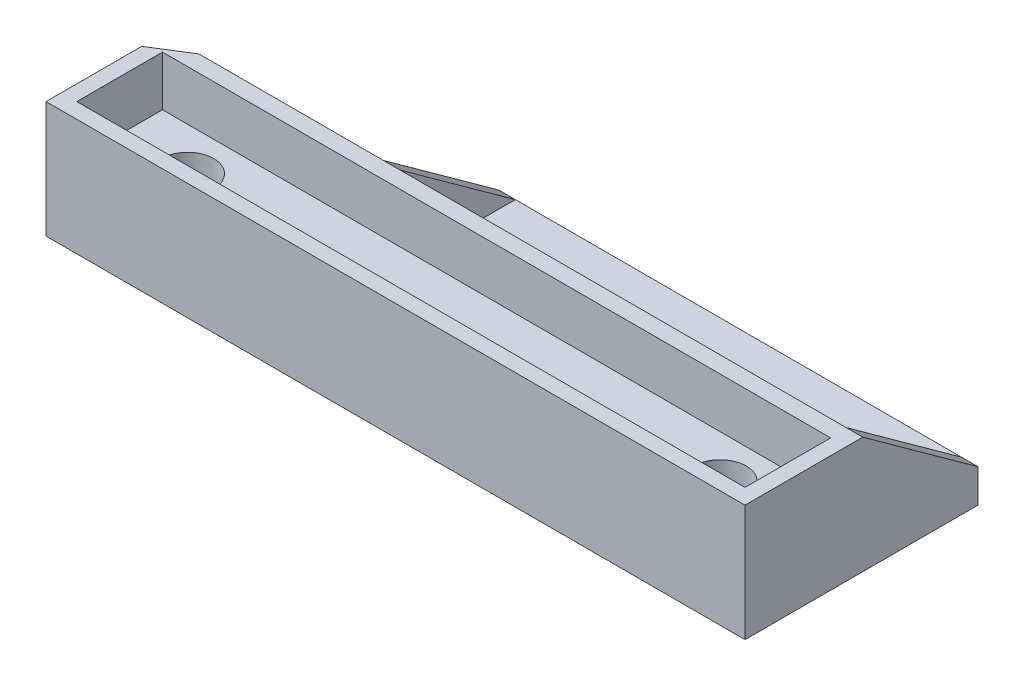
SolidWorks part; units mm, degrees
ref_plane "Front Plane" through (0, 0, 0) normal (0, 0, 1) x (1, 0, 0)
ref_plane "Top Plane" through (0, 0, 0) normal (0, 1, 0) x (1, 0, 0)
ref_plane "Right Plane" through (0, 0, 0) normal (1, 0, 0) x (0, 0, -1)
sketch "Sketch1" plane through (0, 0, 0) normal (0, 1, 0) x (1, 0, 0)
  line L1 (2.0004, 7) -> (42, 7)
  line L2 (0, 5.75) -> (0, 0)
  line L3 (0, 0) -> (42, 0)
  line L4 (42, 7) -> (42, 0)
  line L6 (0, 5.75) -> (2.0004, 7)
  dimension "D1" = 32
  dimension "D2" = 42
  dimension "D3" = 7
  dimension "D4" = 5.75
extrude "Riser" add sketch "Sketch1" along normal blind 7
sketch "Sketch2" plane through (0, 0, 0) normal (0, -1, 0) x (1, 0, 0)
  line L1 (21, 0) -> (21, -7) construction
  line L2 (0, 0) -> (42, 0) construction
  line L4 (42, -7) -> (2.0004, -7) construction
  line L5 (42, 0) -> (42, -7) construction
  circle A0 centre (37, -3.5) radius 1.575
  circle A2 centre (5, -3.5) radius 1.575
  point P6 (42, -3.5)
  dimension "D2" = 3.15
  dimension "D1" = 5
extrude "Mounting Holes" cut sketch "Sketch2" against normal through all
sketch "Sketch3" plane through (0, 7, 0) normal (0, 1, 0) x (1, 0, 0)
  line L5 (42, 7) -> (2.0004, 7) construction
  line L12 (0.925, 6.075) -> (41.075, 6.075)
  line L13 (0.925, 6.075) -> (0.925, 0.925)
  line L14 (0.925, 0.925) -> (41.075, 0.925)
  line L15 (41.075, 6.075) -> (41.075, 0.925)
  line L16 (42, 0) -> (42, 7) construction
  dimension "D1" = 5.15
  dimension "D2" = 40.15
  dimension "D3" = 0.925
  dimension "D4" = 0.925
extrude "Recess" cut sketch "Sketch3" against normal blind 3 contours L12 L15 L14 L13
sketch "Sketch4" plane through (0, 0, 0) normal (0, 1, 0) x (1, 0, 0)
  line L0 (-7.0926, 1.318) -> (28.8348, 23.768) construction
  line L1 (2.0004, 7) -> (42, 7)
  line L2 (42, 7) -> (42, 14)
  line L3 (42, 14) -> (13.2028, 14)
  line L4 (13.2028, 14) -> (2.0004, 7)
  dimension "D1" = 32
  dimension "D2" = 7
extrude "Flange" add sketch "Sketch4" along normal blind 7
sketch "Sketch5" plane through (0, 7, 0) normal (0, 1, 0) x (1, 0, 0)
  line L0 (14.2028, 7.075) -> (14.2028, 14)
  line L1 (42, 14) -> (13.2028, 14) construction
  line L2 (14.2028, 14) -> (41, 14)
  line L3 (41, 14) -> (41, 7.075)
  line L4 (41, 7.075) -> (14.2028, 7.075)
  line L5 (2.1204, 7.075) -> (13.2028, 7.075)
  line L6 (0.925, 6.075) -> (41.075, 6.075) construction
  line L7 (42, 0) -> (42, 14) construction
  line L8 (13.2028, 14) -> (0, 5.75) construction
  line L9 (13.2028, 7.075) -> (13.2028, 14)
  line L10 (13.2028, 14) -> (2.1204, 7.075)
  dimension "D2" = 1
  dimension "D3" = 1
  dimension "D4" = 1
extrude "Flange Cutout" cut sketch "Sketch5" against normal blind 5
sketch "Sketch7" plane through (41, 0, 0) normal (-1, 0, 0) x (0, 0, 1)
  line L0 (-7.075, 7) -> (-14, 2)
  line L1 (-14, 2) -> (-14, 7)
  line L2 (-14, 7) -> (-7.075, 7)
extrude "Angle Cutout" cut sketch "Sketch7" against normal through all and the other way through all
chamfer "Flange Chamfer 1" distance 1 angle 45 1 edges at (27.6014, 2, -7.075)
chamfer "Flange Chamfer 2" distance 1 angle 45 1 edges at (7.6616, 2, -7.075)
